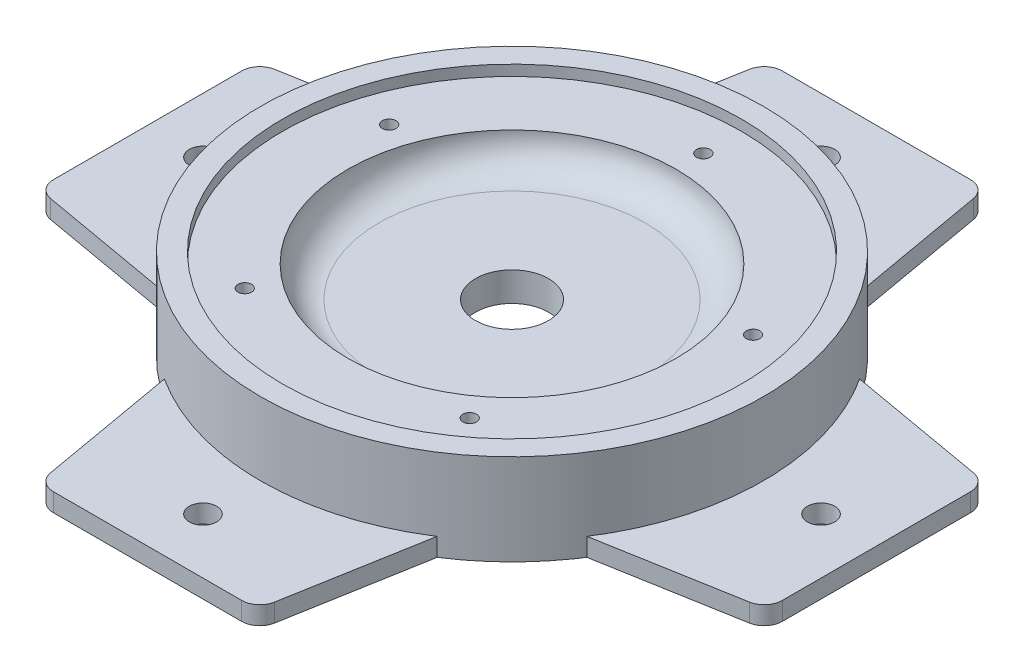
SolidWorks part; units mm, degrees
material "AISI 1020"
ref_plane "Front Plane" through (0, 0, 0) normal (0, 0, 1) x (1, 0, 0)
ref_plane "Top Plane" through (0, 0, 0) normal (0, 1, 0) x (1, 0, 0)
ref_plane "Right Plane" through (0, 0, 0) normal (1, 0, 0) x (0, 0, -1)
sketch "Sketch1" plane through (0, 0, 0) normal (0, 0, 1) x (1, 0, 0)
  line L0 (0, 92.5968) -> (0, -53.0582) construction
  line L2 (87.63, -7.0866) -> (87.63, 24.6634)
  line L4 (87.63, 24.6634) -> (79.9846, 24.6634)
  line L5 (79.9846, 24.6634) -> (79.9846, 20.955)
  line L6 (79.9846, 20.955) -> (57.15, 20.955)
  line L7 (57.15, 20.955) -> (57.15, 10.16)
  line L8 (57.15, 10.16) -> (0, 10.16)
  line L9 (0, 10.16) -> (0, 0)
  line L10 (0, 0) -> (57.15, 0)
  line L11 (57.15, 0) -> (57.15, -7.0866)
  line L12 (57.15, -7.0866) -> (87.63, -7.0866)
  dimension "D1" = 57.15
  dimension "D2" = 87.63
  dimension "D3" = 57.15
  dimension "D4" = 79.9846
  dimension "D5" = 10.16
  dimension "D6" = 20.955
  dimension "D7" = 31.75
  dimension "D8" = 3.7084
revolve "Revolve1" add sketch "Sketch1" angle 360 about L0
hole_wizard "3/16 (0.187) Diameter Hole1" positions "Sketch5" profile "Sketch6" hole size "3/16" standard "ANSI Inch"
sketch "Sketch5" plane through (0, 24.6634, 0) normal (0, 1, 0) x (1, 0, 0)
  point P0 (0, 66.675)
  point P4 (-114.056, -74.738)
  dimension "D1" = 66.675
sketch "Sketch6" plane through (0, 24.6634, -66.675) normal (1, 0, 0) x (0, 0, 1)
  line L0 (0, 0) -> (0, 11.079)
  line L1 (0, 11.079) -> (2.3749, 9.652)
  line L2 (2.3749, 9.652) -> (2.3749, 0)
  line L5 (2.3749, 0) -> (0, 0)
  line L10 (0, 11.079) -> (-2.3749, 9.652) construction
  line L11 (0, -6.35) -> (0, 107.95) construction
  dimension "Hole Dia." = 4.7498
  dimension "Hole Depth" = 9.652
  dimension "Drill Angle" = 118
pattern_circular "CirPattern2" count 5 over 360 about axis through (0, 20.955, 0) along (0, 1, 0) of "3/16 (0.187) Diameter Hole1"
hole_wizard "1 (1) Diameter Hole1" positions "Sketch7" profile "Sketch9" hole size "1" standard "ANSI Inch" end condition through all
sketch "Sketch7" plane through (0, 10.16, 0) normal (0, 1, 0) x (1, 0, 0)
  point P0 (0, 0)
sketch "Sketch9" plane through (0, 10.16, 0) normal (1, 0, 0) x (0, 0, 1)
  line L0 (0, 0) -> (0, 17.2466)
  line L1 (0, 17.2466) -> (12.7, 17.2466)
  line L2 (12.7, 17.2466) -> (12.7, 0)
  line L5 (12.7, 0) -> (0, 0)
  line L11 (0, -6.35) -> (0, 107.95) construction
  dimension "Thru Hole Dia." = 25.4
  dimension "Thru Hole Depth" = 17.2466
sketch "Sketch14" plane through (0, 20.955, 0) normal (0, -1, 0) x (1, 0, 0)
  circle A0 centre (0, 0) radius 19.05
  dimension "D1" = 38.1
sketch "Sketch15" plane through (0, -7.0866, 0) normal (0, -1, 0) x (1, 0, 0)
  line L4 (0, 0) -> (-157.4172, 0) construction
  line L6 (-127, -38.1) -> (-73.633, -47.51)
  line L9 (-127, 38.1) -> (-127, -38.1)
  line L10 (0, -17.4625) -> (0, 17.4625) construction
  line L11 (-127, 38.1) -> (-73.633, 47.51)
  circle A0 centre (0, 0) radius 87.63 construction
  arc A1 (-73.633, 47.51) -> (-73.633, -47.51) centre (0, 0) ccw
  dimension "D1" = 76.2
  dimension "D4" = 127
  dimension "D5" = 100
extrude "Boss-Extrude1" add sketch "Sketch15" against normal blind 6.35 separate body
fillet "Fillet2" radius 6.35 2 edges at (-127, -3.9116, -38.1) (-127, -3.9116, 38.1)
hole_wizard "3/8 (0.375) Diameter Hole1" positions "Sketch16" profile "Sketch17" hole size "3/8" standard "ANSI Inch"
sketch "Sketch16" plane through (0, -0.7366, 0) normal (0, 1, 0) x (1, 0, 0)
  point P0 (-107.696, 0)
  dimension "D1" = 107.696
sketch "Sketch17" plane through (-107.696, -0.7366, 0) normal (1, 0, 0) x (0, 0, 1)
  line L0 (0, 0) -> (0, 28.2616)
  line L1 (0, 28.2616) -> (4.7625, 25.4)
  line L2 (4.7625, 25.4) -> (4.7625, 0)
  line L5 (4.7625, 0) -> (0, 0)
  line L10 (0, 28.2616) -> (-4.7625, 25.4) construction
  line L11 (0, -6.35) -> (0, 107.95) construction
  dimension "Hole Dia." = 9.525
  dimension "Hole Depth" = 25.4
  dimension "Drill Angle" = 118
pattern_circular "CirPattern4" count 4 over 360 about axis through (0, 24.6634, 0) along (0, 1, 0) of bodies 121
fillet "Fillet3" radius 10.795 2 edges at (0, 0, 57.15) (0, 10.16, 57.15)
